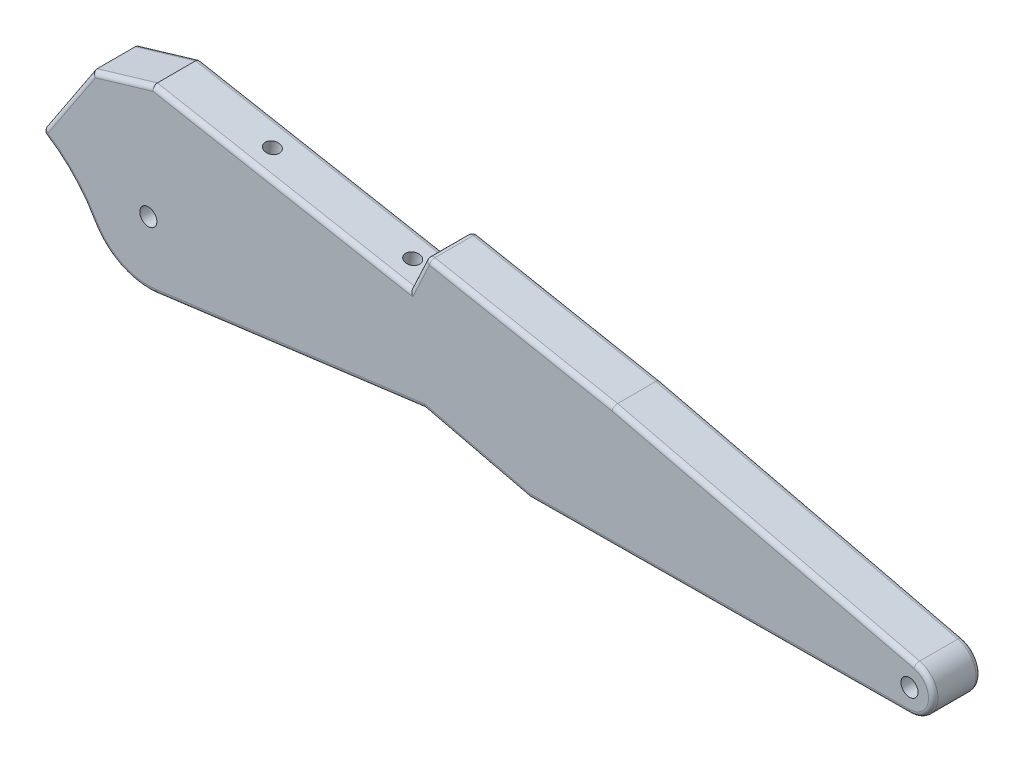
SolidWorks part; units mm, degrees
ref_plane "Front Plane" through (0, 0, 0) normal (0, 0, 1) x (1, 0, 0)
ref_plane "Top Plane" through (0, 0, 0) normal (0, 1, 0) x (1, 0, 0)
ref_plane "Right Plane" through (0, 0, 0) normal (1, 0, 0) x (0, 0, -1)
sketch "Sketch1" plane through (0, 0, 0) normal (0, 0, 1) x (1, 0, 0)
  line L1 (0.0486, -6.3498) -> (-101.5514, -7.1275)
  line L2 (-101.5514, -7.1275) -> (-129.54, -0.456)
  line L6 (-128.905, 34.925) -> (-133.35, 25.4)
  line L7 (-200.977, -9.7973) -> (-129.54, -0.456)
  line L8 (-133.35, 25.4) -> (-202.0358, 38.1)
  line L9 (-202.0358, 38.1) -> (-218.1154, 33.3375)
  line L10 (-128.905, 34.925) -> (-79.1726, 25.4)
  line L11 (-79.1726, 25.4) -> (-128.905, 34.925) construction
  line L12 (-79.1726, 25.4) -> (1.4724, 6.1769)
  line L13 (-129.5991, 33.4375) -> (-133.35, 25.4) construction
  line L17 (-133.35, 25.4) -> (-202.0358, 38.1) construction
  line L18 (-17.145, -27.2472) -> (-129.54, -0.456) construction
  line L19 (-200.977, -9.7973) -> (-129.54, -0.456) construction
  line L20 (-107.0451, 30.7383) -> (-127.6185, 34.6786) construction
  line L21 (-180.2576, 44.5503) -> (-218.1154, 33.3375) construction
  line L22 (-231.775, 12.7) -> (-218.1154, 33.3375)
  line L23 (-218.1154, 33.3375) -> (-273.7845, -50.7694) construction
  line L24 (-17.145, -27.2472) -> (-129.54, -0.456) construction
  line L29 (-79.1726, 25.4) -> (1.4724, 6.1769) construction
  line L31 (-129.54, -0.456) -> (-200.977, -9.7973) construction
  circle A0 centre (0, 0) radius 2.286
  arc A1 (0.0486, -6.3498) -> (1.4724, 6.1769) centre (0, 0) ccw
  circle A2 centre (-203.2, 7.203) radius 2.286
  arc A6 (-218.1154, -1.2518) -> (-200.977, -9.7973) centre (-203.2, 7.203) ccw
  circle A7 centre (-203.2, 7.203) radius 2.286 construction
  arc A8 (4.6019, -4.3755) -> (1.4724, 6.1769) centre (0, 0) ccw construction
  arc A10 (-200.977, -9.7973) -> (-218.1154, -1.2518) centre (-203.2, 7.203) ccw construction
  arc A11 (-218.1154, -1.2518) -> (-231.775, 12.7) centre (-251.2606, -20.0402) ccw
  arc A12 (-231.775, 12.7) -> (-218.1154, -1.2518) centre (-251.2606, -20.0402) ccw construction
  point P17 (105.4504, -19.602)
  point P18 (-71.2573, 0.0759)
  dimension "D1" = 4.572
  dimension "D2" = 101.6
extrude "Boss-Extrude1" add sketch "Sketch1" along normal blind 12.7
fillet "Fillet1" radius 1.27 26 edges at (-165.2585, -5.1266, 12.7) (-210.8505, -8.1405, 12.7) (-38.8501, 15.7885, 12.7) (-224.0363, 6.614, 0) (-210.8505, -8.1405, 0) (-50.7514, -6.7387, 0) (-224.0363, 6.614, 12.7) (-224.9452, 23.0188, 12.7) (-210.0756, 35.7188, 12.7) (-167.6929, 31.75, 12.7) (-131.1275, 30.1625, 0) (-131.1275, 30.1625, 12.7) (-104.0388, 30.1625, 12.7) (-115.5457, -3.7917, 12.7) (-50.7514, -6.7387, 12.7) (-210.0756, 35.7188, 0) (-224.9452, 23.0188, 0) (-167.6929, 31.75, 0) (-128.905, 34.925, 6.35) (-165.2585, -5.1266, 0) (-115.5457, -3.7917, 0) (-38.8501, 15.7885, 0) (-104.0388, 30.1625, 0) (6.3094, -0.7171, 12.7) (6.3094, -0.7171, 0) (-231.775, 12.7, 6.35)
sketch "Sketch2" plane through (0, 0, 0) normal (0, 0, -1) x (-1, 0, 0)
  circle A0 centre (0, 0) radius 5.2387
  dimension "D1" = 10.4775
extrude "Cut-Extrude1" cut sketch "Sketch2" against normal blind 3.9688
sketch "Sketch3" plane through (0.1329, 0.719, 0) normal (0.1818, 0.9833, 0) x (0.9833, -0.1818, 0)
  circle A0 centre (-179.5561, -6.35) radius 1.905
  circle A1 centre (-141.4561, -6.35) radius 1.905
  dimension "D1" = 3.81
extrude "Cut-Extrude2" cut sketch "Sketch3" against normal blind 12.7
sketch "Sketch4" plane through (-167.0137, 110.5438, 0) normal (-0.8339, 0.5519, 0) x (0, 0, 1)
  line L0 (0, -116.025) -> (0, -93.0484) construction
  line L1 (1.27, -117.295) -> (11.43, -117.295) construction
  circle A0 centre (6.35, -110.945) radius 1.905
  dimension "D1" = 3.81
  dimension "D2" = 6.35
  dimension "D3" = 6.35
extrude "Cut-Extrude3" cut sketch "Sketch4" against normal blind 12.7
